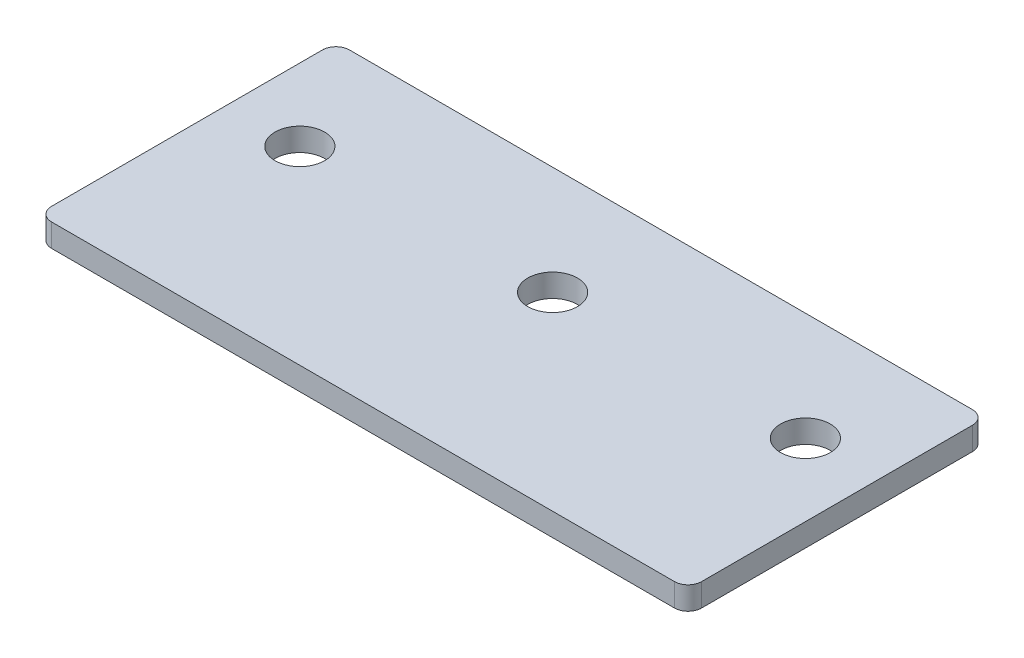
SolidWorks part; units mm, degrees
material "AISI 304 Stainless Steel"
ref_plane "Front Plane" through (0, 0, 0) normal (0, 0, 1) x (1, 0, 0)
ref_plane "Top Plane" through (0, 0, 0) normal (0, 1, 0) x (1, 0, 0)
ref_plane "Right Plane" through (0, 0, 0) normal (1, 0, 0) x (0, 0, -1)
ref_axis "Axis1" through (0, 0, -88.99) along (0, 0, 1)
ref_axis "Axis2" through (0, -55, 0) along (0, 1, 0)
ref_axis "Axis3" through (-88.99, 0, 0) along (1, 0, 0)
sketch "Sketch1" plane through (0, 0, 0) normal (0, 1, 0) x (1, 0, 0)
  line L0 (0, 0) -> (0, 4.5) construction
  line L1 (36, -16.5) -> (-36, -16.5)
  line L2 (36, -16.5) -> (36, 16.5)
  line L3 (36, 16.5) -> (-36, 16.5)
  line L4 (-36, -16.5) -> (-36, 16.5)
  line L5 (36, -16.5) -> (-36, 16.5) construction
  line L6 (36, 16.5) -> (-36, -16.5) construction
  circle A0 centre (-28, 4.5) radius 2.75
  circle A1 centre (0, 4.5) radius 2.75
  circle A2 centre (28, 4.5) radius 2.75
  point P0 (0, 0)
  dimension "D1" = 5.5
  dimension "D2" = 12
  dimension "D3" = 21
  dimension "D4" = 56
  dimension "D5" = 72
extrude "Boss-Extrude1" add sketch "Sketch1" along normal blind 2.54
fillet "Fillet1" radius 1.5 4 edges at (-36, 1.27, -16.5) (36, 1.27, -16.5) (36, 1.27, 16.5) (-36, 1.27, 16.5)
